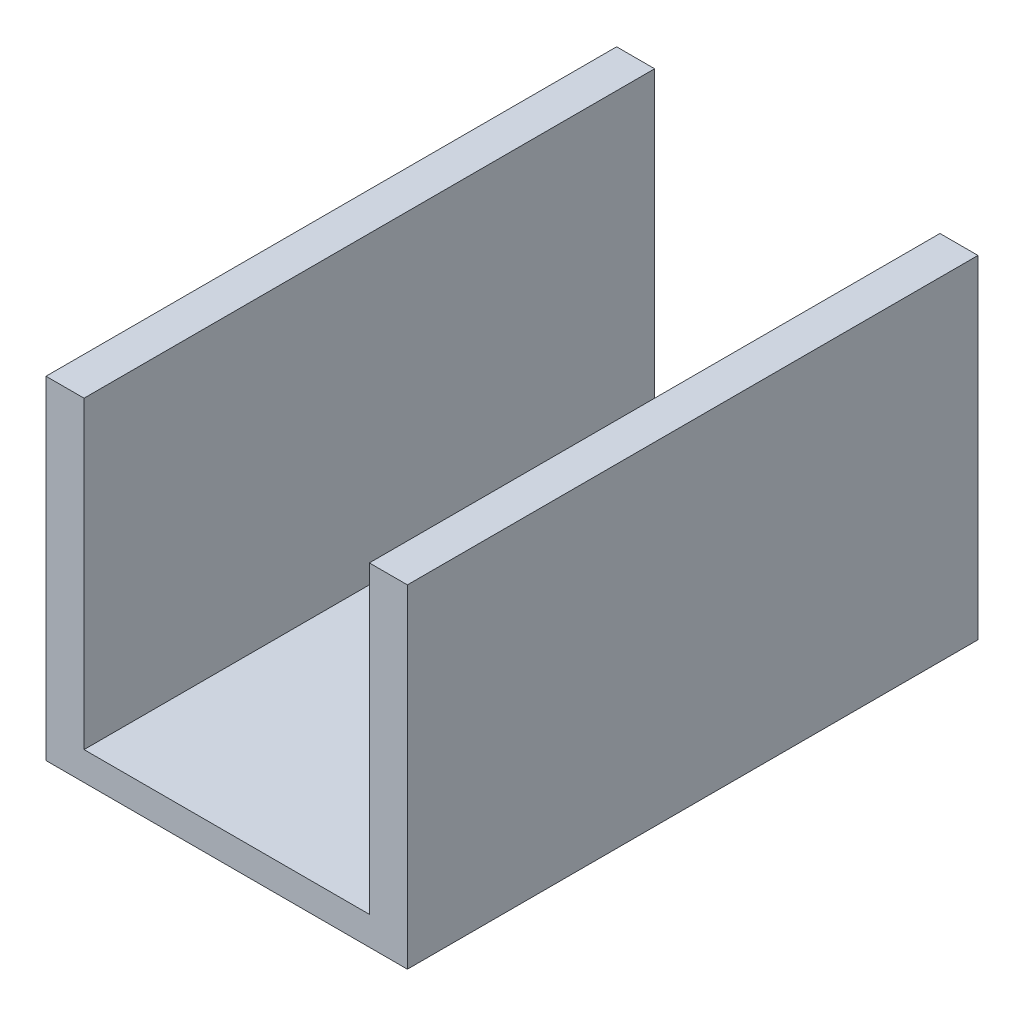
SolidWorks part; units mm, degrees
material "PLA"
ref_plane "Front Plane" through (0, 0, 0) normal (0, 0, 1) x (1, 0, 0)
ref_plane "Top Plane" through (0, 0, 0) normal (0, 1, 0) x (1, 0, 0)
ref_plane "Right Plane" through (0, 0, 0) normal (1, 0, 0) x (0, 0, -1)
sketch "Sketch2" plane through (0, 0, 0) normal (0, 0, 1) x (1, 0, 0)
  line L0 (-30, 0) -> (30, 0)
  line L1 (-30, 0) -> (-30, 64)
  line L2 (-30, 64) -> (-38, 64)
  line L3 (-38, 64) -> (-38, -6)
  line L7 (30, 64) -> (30, 0)
  line L8 (-38, -6) -> (38, -6)
  line L9 (38, -6) -> (38, 64)
  line L10 (38, 64) -> (30, 64)
  point P4 (0, 0)
  dimension "D1" = 60
  dimension "D2" = 8
  dimension "D3" = 8
  dimension "D4" = 70
  dimension "D5" = 6
  dimension "D6" = 70
extrude "Boss-Extrude1" add sketch "Sketch2" along normal mid plane 120
